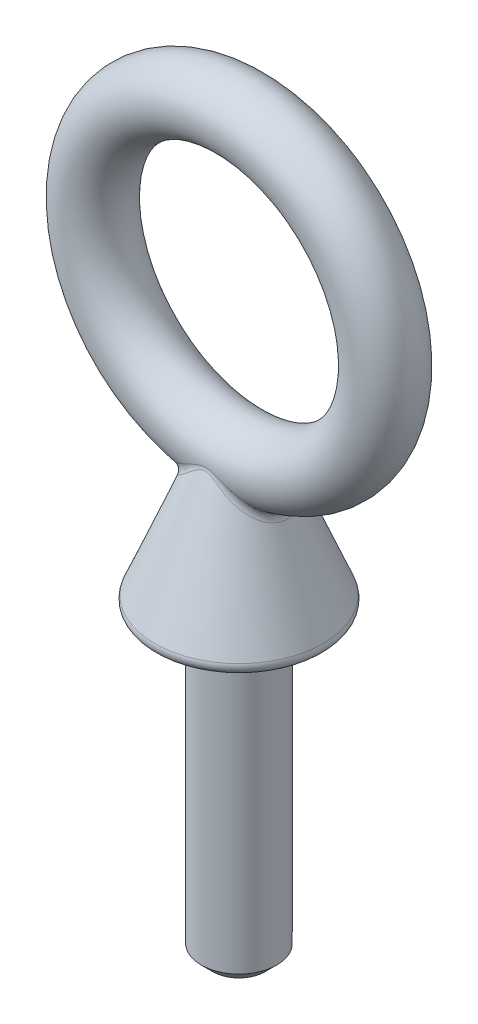
SolidWorks part; units mm, degrees
ref_plane "Front Plane" through (0, 0, 0) normal (0, 0, 1) x (1, 0, 0)
ref_plane "Top Plane" through (0, 0, 0) normal (0, 1, 0) x (1, 0, 0)
ref_plane "Right Plane" through (0, 0, 0) normal (1, 0, 0) x (0, 0, -1)
sketch "Sketch1" plane through (0, 0, 0) normal (0, 0, 1) x (1, 0, 0)
  line L0 (0, -15.0812) -> (0, -49.2125) construction
  line L1 (-3.175, -49.2125) -> (3.175, -49.2125) construction
  line L2 (3.3125, -49.1331) -> (3.3125, -50.4031) construction
  line L3 (0, -15.0812) -> (0, -9.525) construction
  line L4 (-7.1437, -23.8125) -> (7.1438, -23.8125) construction
  line L5 (3.3125, -50.4031) -> (2.2126, -49.7681) construction
  line L6 (2.2126, -49.7681) -> (3.3125, -49.1331) construction
  line L7 (2.2126, -49.7681) -> (2.3501, -49.7681) construction
  line L8 (3.3125, -49.7681) -> (3.175, -49.7681) construction
  line L9 (2.3501, -49.8475) -> (2.3501, -49.6887) construction
  line L10 (3.175, -50.3238) -> (3.175, -49.2125) construction
  line L11 (3.2437, -50.3634) -> (3.2437, -49.1728) construction
  circle A0 centre (0, 0) radius 15.0813 construction
  circle A1 centre (0, 12.3031) radius 2.7781 construction
  circle A2 centre (0, 0) radius 9.525 construction
  point P7 (0, -15.0812)
  point P9 (0, -23.8125)
  point P10 (0, 15.0812)
  point P11 (0, 9.525)
  point P14 (0, -49.2125)
  point P17 (0, 0)
  point P19 (0, -12.3031)
  point P21 (0, -23.8125)
  point P32 (2.3501, -49.7681)
  point P35 (3.175, -49.7681)
  point P38 (3.2437, -49.7681)
  dimension "Pitch" = 1.27
  dimension "D1" = 0.1588
sketch "Sketch2" plane through (0, 0, 0) normal (0, 1, 0) x (1, 0, 0)
  circle A0 centre (0, 0) radius 3.175
extrude "Boss-Extrude1" add sketch "Sketch2" against normal up to vertex (49.2125 mm away) from vertex up to point (0, -49.2125, 0) starting at point (0, -23.8125, 0)
sketch "Sketch3" [suppressed] plane through (0, -49.2125, 0) normal (0, -1, 0) x (1, 0, 0)
  circle A1 centre (0, 0) radius 3.175
  circle A2 centre (0, 0) radius 3.175
  point P0 (3.175, 0)
  point P1 (0, -3.175)
  dimension "D1" = 0
sketch "Sketch4" [suppressed] plane through (0, 0, 0) normal (0, 0, 1) x (1, 0, 0)
  line L0 (2.3501, -49.6887) -> (2.3501, -49.8475)
  line L1 (2.3501, -49.8475) -> (3.2437, -50.3634)
  line L2 (3.2437, -50.3634) -> (3.2437, -49.1728)
  line L3 (3.2437, -49.1728) -> (2.3501, -49.6887)
sketch "Sketch5" plane through (0, -49.2125, 0) normal (0, -1, 0) x (1, 0, 0)
  circle A0 centre (0, 0) radius 2.2126
extrude "Cut-Extrude1" cut sketch "Sketch5" against normal through all draft 45 flip side to cut
sketch "Sketch6" plane through (0, 0, 0) normal (1, 0, 0) x (0, 0, -1)
  circle A0 centre (0, 12.3031) radius 2.7781
ref_axis "Axis1" through (0, 0, -7.6398) along (0, 0, 1)
revolve "Revolve1" add sketch "Sketch6" angle 360 about axis through (0, 0, -7.6398) along (0, 0, 1)
sketch "Sketch8" plane through (0, 0, 0) normal (0, 0, 1) x (1, 0, 0)
  line L0 (0, -23.8125) -> (0, -12.3031)
  line L1 (0, -12.3031) -> (-2.7781, -12.3031)
  line L2 (-6.4492, -23.8125) -> (-7.1437, -23.8125) construction
  line L3 (-7.1437, -23.8125) -> (-7.1437, -23.118) construction
  line L4 (0, -23.8125) -> (7.1437, -23.8125) construction
  line L5 (-7.1437, -23.8125) -> (7.1438, -23.8125) construction
  line L6 (-7.0921, -22.8551) -> (-2.7781, -12.3031)
  line L7 (-7.1437, -23.8125) -> (0, -23.8125) construction
  line L9 (-6.4492, -23.8125) -> (0, -23.8125)
  arc A0 (-7.0921, -22.8551) -> (-6.4492, -23.8125) centre (-6.4492, -23.118) ccw
  circle A1 centre (0, -12.3031) radius 2.7781 construction
  dimension "D1" = 0.6945
revolve "Revolve2" add sketch "Sketch8" angle 360 about L0
fillet "Fillet1" radius 0.6945 1 edges at (3.2544, -14.2744, 1.5013)
sketch "SketchX" plane through (0, 0, 0) normal (1, 0, 0) x (0, 0, -1)
  line L0 (3.175, -49.2125) -> (3.175, -46.0375) construction
  line L1 (0, -49.2125) -> (3.175, -49.2125) construction
  dimension "D1" = 3.175
  dimension "D2" = 3.175
ref_axis "Center Axis 1" through (0, 21.5506, 0) along (0, -1, 0)
ref_axis "Center Axis 2" through (0, 0, -7.6398) along (0, 0, 1)
curve "Helix/Spiral1" [suppressed] pitch 1.27 height 26.67 turns 21 parameters "Pitch"=1.27
ref_plane "Plane1" [suppressed] through (0, -23.8125, 0) normal (0, -1, 0) x (1, 0, 0)
split "Split1" [suppressed] bodies to split 109
sweep "Cut-Sweep1" [suppressed] cut profiles "Sketch4" path "Helix/Spiral1"
sketch "Sketch9" [suppressed] plane through (0, -23.8125, 0) normal (0, -1, 0) x (1, 0, 0)
  line L0 (-7.1437, 0) -> (7.1438, 0) construction
  circle A0 centre (0, 0) radius 3.175
extrude "Boss-Extrude2" [suppressed] add sketch "Sketch9" along normal blind 2.54 draft 45
ref_axis "Axis2" through (0, -52.4272, 0) along (0, 1, 0)
equation "\"D3@Helix/Spiral1\" = \"Pitch@Helix/Spiral1\" + \"Thread Lg.@Sketch1\""
equation "\"D1@Sketch8\" = \"A@Sketch1\" / 8"
equation "\"D1@Fillet1\" = \"A@Sketch1\" / 8"
equation "\"D1@SketchX\"= \"Pitch@Helix/Spiral1\"*2.5"
equation "\"D1@Sketch1\"=\"Pitch@Sketch1\"/8"
equation "\"Pitch@Helix/Spiral1\"=\"Pitch@Sketch1\""
equation "\"D2@SketchX\" = \"Thread OD@Sketch1\" / 2"
